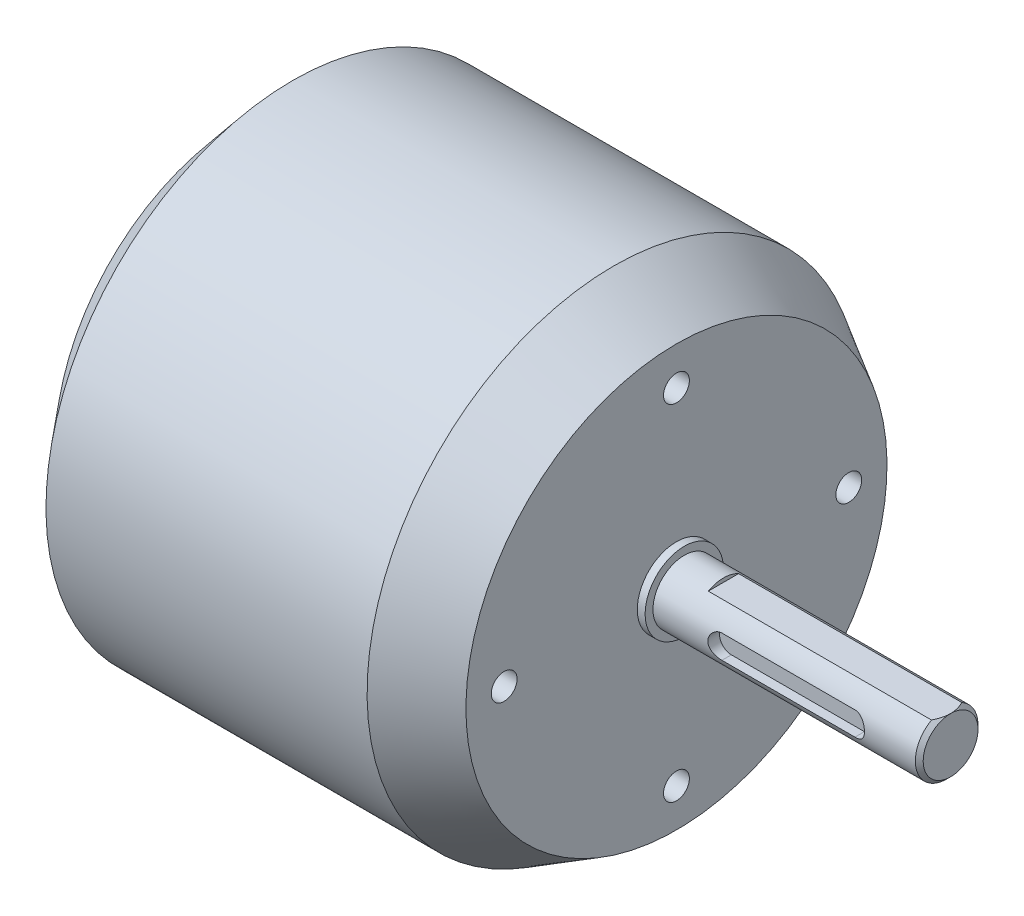
SolidWorks part; units mm, degrees
ref_plane "Normal Z (Oben)" through (0, 0, 0) normal (0, 0, 1) x (1, 0, 0)
ref_plane "Normal Y" through (0, 0, 0) normal (0, 1, 0) x (1, 0, 0)
ref_plane "Normal X" through (0, 0, 0) normal (1, 0, 0) x (0, 0, -1)
sketch "Skizze1" plane through (0, 0, 0) normal (0, 0, 1) x (1, 0, 0)
  line L0 (27.5, 0) -> (-27.5, 0)
  line L1 (-27.5, 0) -> (-27.5, 24.3495)
  line L2 (-27.5, 24.3495) -> (-21.5, 31.5)
  line L3 (-21.5, 31.5) -> (19.5, 31.5)
  line L4 (19.5, 31.5) -> (27.5, 26.8812)
  line L5 (27.5, 26.8812) -> (27.5, 0)
  point P5 (0, 0)
  dimension "D1" = 55
  dimension "D2" = 31.5
  dimension "D3" = 120
  dimension "D4" = 8
  dimension "D5" = 6
  dimension "D6" = 140
revolve "Rotation1" add sketch "Skizze1" angle 360 about L0
sketch "Skizze2" plane through (27.5, 0, 0) normal (1, 0, 0) x (0, 0, -1)
  circle A0 centre (0, 0) radius 4
  circle A1 centre (0, 0) radius 5
  dimension "D1" = 8
  dimension "D2" = 10
extrude "Aufsatz-Linear austragen1" add sketch "Skizze2" along normal blind 1
extrude "Aufsatz-Linear austragen2" add sketch "Skizze2<2>" along normal blind 35 contours A0 region at (27.5, 0, 0)
sketch "Skizze2<2>" plane through (27.5, 0, 0) normal (1, 0, 0) x (0, 0, -1) same geometry as "Skizze2"
hole_wizard "M4 Gewindebohrung1" positions "Skizze4" profile "Skizze5" tap size "M4" standard "DIN"
sketch "Skizze4" plane through (27.5, 0, 0) normal (1, 0, 0) x (0, 0, -1)
  line L1 (0, -22) -> (-22, 0) construction
  line L2 (0, -22) -> (22, 0) construction
  line L3 (22, 0) -> (0, 22) construction
  line L4 (-22, 0) -> (0, 22) construction
  line L5 (0, -22) -> (0, 22) construction
  point P2 (0, 22)
  point P61 (0, -22)
  point P62 (22, 0)
  point P63 (-22, 0)
  point P81 (0, 0)
  point P83 (18.7107, 11.5719)
  point P84 (12.516, 8.6581)
  point P85 (15.5563, 15.5563)
  point P86 (20.9032, 6.8596)
  dimension "D1" = 44
sketch "Skizze5" plane through (27.5, 22, 0) normal (0, 1, 0) x (0, 0, -1)
  line L0 (0, 0) -> (0, 10.9914)
  line L1 (0, 10.9914) -> (1.65, 10)
  line L2 (1.65, 10) -> (1.65, 0)
  line L5 (1.65, 0) -> (0, 0)
  line L10 (0, 10.9914) -> (-1.65, 10) construction
  line L11 (0, -6.35) -> (0, 107.95) construction
  dimension "Bohrerdurchmesser" = 3.3
  dimension "Bohrungstiefe" = 10
  dimension "Spitzenwinkel" = 118
cosmetic thread "Bohrungsgewinde1"
cosmetic thread "Bohrungsgewinde2"
cosmetic thread "Bohrungsgewinde3"
cosmetic thread "Bohrungsgewinde4"
ref_plane "Ebene1" through (0, 0, 4) normal (0, 0, 1) x (1, 0, 0)
sketch "Skizze6" plane through (0, 0, 4) normal (0, 0, 1) x (1, 0, 0)
  line L0 (37.0062, 0) -> (53.9937, 0) construction
  line L1 (37.0062, 1.5063) -> (53.9937, 1.5063)
  line L2 (37.0062, -1.5063) -> (53.9937, -1.5062)
  line L3 (45.5, 4) -> (45.5, -3.9969) construction
  line L4 (62.5, 4) -> (28.5, 4) construction
  line L6 (55.5, -1.5044) -> (35.5, -1.5044) construction
  line L7 (55.5, -1.5044) -> (55.5, 1.5044) construction
  line L8 (55.5, 1.5044) -> (35.5, 1.5044) construction
  line L9 (35.5, -1.5044) -> (35.5, 1.5044) construction
  line L10 (55.5, -1.5044) -> (35.5, 1.5044) construction
  line L11 (55.5, 1.5044) -> (35.5, -1.5044) construction
  arc A0 (37.0062, 1.5063) -> (37.0062, -1.5063) centre (37.0062, 0) ccw
  arc A1 (53.9937, -1.5062) -> (53.9937, 1.5063) centre (53.9937, 0) ccw
  point P3 (45.5, 0)
  point P9 (45.5, 0)
  dimension "D2" = 20
  dimension "D1" = 3.0125
extrude "Schnitt-Linear austragen1" cut sketch "Skizze6" against normal blind 1.5
sketch "Skizze7" plane through (62.5, 0, 0) normal (1, 0, 0) x (0, 0, -1)
  line L0 (0, 0) -> (0, 4) construction
  line L2 (-4, 7.1414) -> (4, 7.1414)
  line L3 (-4, 7.1414) -> (-4, 3.5)
  line L4 (-4, 3.5) -> (4, 3.5)
  line L5 (4, 7.1414) -> (4, 3.5)
  line L6 (0, 4) -> (-4, 4) construction
  circle A0 centre (0, 0) radius 4 construction
  point P10 (0, 3.5)
  dimension "D1" = 0.5
extrude "Schnitt-Linear austragen2" cut sketch "Skizze7" against normal offset from surface (29 mm away) 5 up to face at (28.5, 5, 0)
chamfer "Fase1" distance 0.5 angle 45 1 edges at (62.5, -4, 0)
sketch "Skizze8" plane through (0, 0, 0) normal (0, 0, 1) x (1, 0, 0)
  line L0 (33.5, 4) -> (28.5, 4) construction
  line L1 (28.7, 4) -> (29.5, 4)
  line L2 (28.7, 4) -> (28.7, 3.8)
  line L3 (28.7, 3.8) -> (29.5, 3.8)
  line L4 (29.5, 4) -> (29.5, 3.8)
  line L5 (28.5, -4) -> (28.5, 4) construction
  dimension "D1" = 0.8
  dimension "D2" = 0.2
  dimension "D3" = 0.2
ref_axis "Achse1" through (62, 0, 0) along (-1, 0, 0)
revolve "Schnitt-Rotation1" [suppressed] cut sketch "Skizze8" angle 360 about axis through (62, 0, 0) along (-1, 0, 0)
